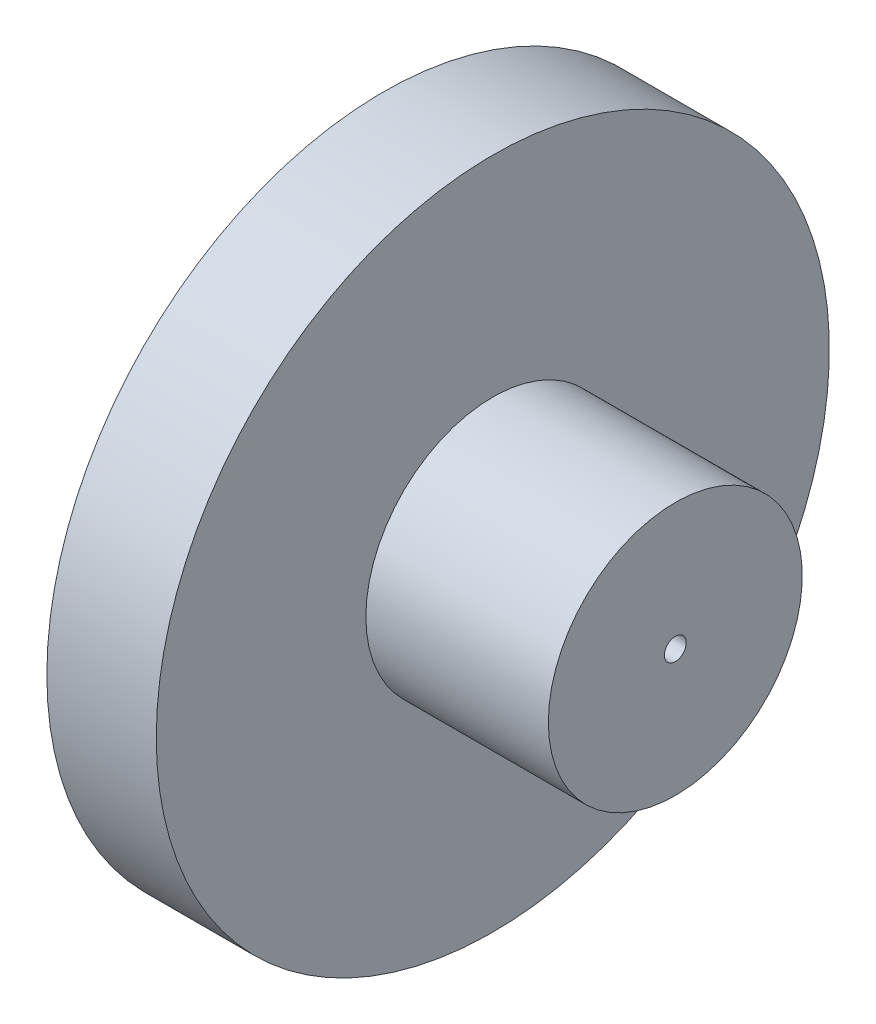
SolidWorks part; units mm, degrees
ref_plane "Front Plane" through (0, 0, 0) normal (0, 0, 1) x (1, 0, 0)
ref_plane "Top Plane" through (0, 0, 0) normal (0, 1, 0) x (1, 0, 0)
ref_plane "Right Plane" through (0, 0, 0) normal (1, 0, 0) x (0, 0, -1)
sketch "Sketch1" plane through (0, 0, 0) normal (0, 0, 1) x (1, 0, 0)
  line L0 (-103.5923, 5) -> (-103.5923, 32.8101)
  line L1 (-103.5923, 32.8101) -> (-25, 32.8101)
  line L2 (-25, 32.8101) -> (-25, 153.8101)
  line L3 (-25, 153.8101) -> (25, 153.8101)
  line L4 (25, 153.8101) -> (25, 58.0228)
  line L5 (25, 58.0228) -> (108.4077, 58.0228)
  line L6 (108.4077, 58.0228) -> (108.4077, 5)
  line L7 (108.4077, 5) -> (-103.5923, 5)
  line L8 (-37.412, 0) -> (19.8786, 0) construction
  dimension "D1" = 121
  dimension "D2" = 212
  dimension "D3" = 50
  dimension "D4" = 5
revolve "Revolve1" add sketch "Sketch1" angle 360 about L8
